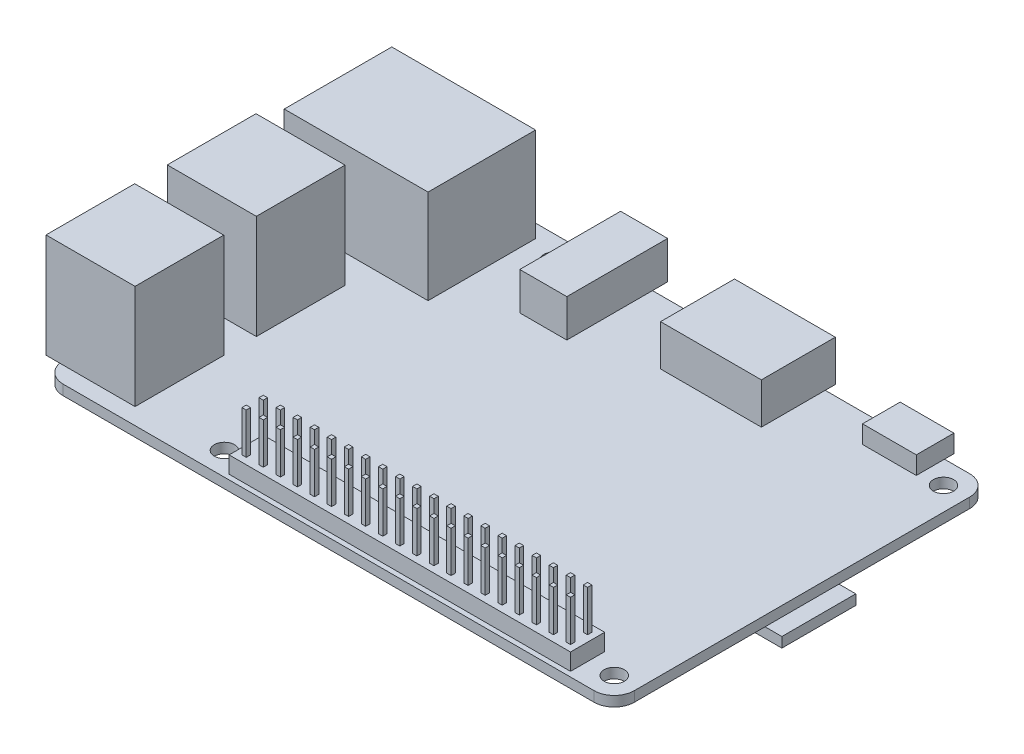
SolidWorks part; units mm, degrees
ref_plane "Front Plane" through (0, 0, 0) normal (0, 0, 1) x (1, 0, 0)
ref_plane "Top Plane" through (0, 0, 0) normal (0, 1, 0) x (1, 0, 0)
ref_plane "Right Plane" through (0, 0, 0) normal (1, 0, 0) x (0, 0, -1)
sketch "Sketch1" plane through (0, 0, 0) normal (0, 1, 0) x (1, 0, 0)
  line L0 (39.05, 24.5) -> (39.05, 27.95) construction
  line L1 (-39.5, -27.95) -> (39.5, -27.95)
  line L2 (-42.5, -24.95) -> (-42.5, 24.95)
  line L3 (-39.5, 27.95) -> (39.5, 27.95)
  line L4 (42.5, -24.95) -> (42.5, 24.95)
  line L5 (-42.5, -27.95) -> (42.5, 27.95) construction
  line L6 (-42.5, 27.95) -> (42.5, -27.95) construction
  line L7 (-18.95, -24.5) -> (39.05, -24.5) construction
  line L8 (-18.95, -24.5) -> (-18.95, 24.5) construction
  line L9 (-18.95, 24.5) -> (39.05, 24.5) construction
  line L10 (39.05, -24.5) -> (39.05, 24.5) construction
  line L11 (39.05, -24.5) -> (39.05, -27.95) construction
  line L12 (39.05, 24.5) -> (42.5, 24.5) construction
  circle A0 centre (-18.95, 24.5) radius 1.5
  circle A1 centre (39.05, 24.5) radius 1.5
  circle A2 centre (39.05, -24.5) radius 1.5
  circle A3 centre (-18.95, -24.5) radius 1.5
  arc A4 (39.5, 27.95) -> (42.5, 24.95) centre (39.5, 24.95) cw
  arc A5 (39.5, -27.95) -> (42.5, -24.95) centre (39.5, -24.95) ccw
  arc A6 (-39.5, -27.95) -> (-42.5, -24.95) centre (-39.5, -24.95) cw
  arc A7 (-42.5, 24.95) -> (-39.5, 27.95) centre (-39.5, 24.95) cw
  point P0 (0, 0)
  point P6 (0, 0)
  dimension "D1" = 3
  dimension "D6" = 3
  dimension "D2" = 85
  dimension "D3" = 55.9
  dimension "D4" = 49
  dimension "D5" = 58
extrude "Boss-Extrude1" add sketch "Sketch1" along normal blind 1.5
sketch "Sketch2" plane through (0, 0, 0) normal (0, -1, 0) x (1, 0, 0)
  line L0 (0, 0) -> (37.25, 0) construction
  line L1 (29.5, -5.5) -> (45, -5.5)
  line L2 (29.5, -5.5) -> (29.5, 5.5)
  line L3 (29.5, 5.5) -> (45, 5.5)
  line L4 (45, -5.5) -> (45, 5.5)
  line L5 (29.5, -5.5) -> (45, 5.5) construction
  line L6 (29.5, 5.5) -> (45, -5.5) construction
  line L7 (42.5, 24.95) -> (42.5, -24.95) construction
  point P0 (37.25, 0)
  dimension "D1" = 11
  dimension "D2" = 2.5
  dimension "D3" = 15.5
extrude "Boss-Extrude2" add sketch "Sketch2" along normal blind 1.5
sketch "Sketch3" plane through (0, 1.5, 0) normal (0, 1, 0) x (1, 0, 0)
  line L0 (39.5, 27.95) -> (-39.5, 27.95) construction
  line L1 (-44.5, 25.95) -> (-23.1, 25.95)
  line L2 (-44.5, 25.95) -> (-44.5, 9.95)
  line L3 (-44.5, 9.95) -> (-23.1, 9.95)
  line L4 (-23.1, 25.95) -> (-23.1, 9.95)
  line L5 (-42.5, 24.95) -> (-42.5, -24.95) construction
  dimension "D1" = 21.4
  dimension "D2" = 16
  dimension "D3" = 2
  dimension "D4" = 2
extrude "Boss-Extrude3" add sketch "Sketch3" along normal blind 14
sketch "Sketch4" plane through (0, 1.5, 0) normal (0, 1, 0) x (1, 0, 0)
  line L0 (-42.5, 9.95) -> (-23.1, 9.95) construction
  line L1 (-44.5, 5.75) -> (-31.25, 5.75)
  line L2 (-44.5, 5.75) -> (-44.5, -7.45)
  line L3 (-44.5, -7.45) -> (-31.25, -7.45)
  line L4 (-31.25, 5.75) -> (-31.25, -7.45)
  line L5 (-44.5, -12.3) -> (-31.25, -12.3)
  line L6 (-44.5, -12.3) -> (-44.5, -25.5)
  line L7 (-44.5, -25.5) -> (-31.25, -25.5)
  line L8 (-31.25, -12.3) -> (-31.25, -25.5)
  line L9 (-44.5, 25.95) -> (-44.5, 9.95) construction
  dimension "D1" = 4.2
  dimension "D2" = 13.2
  dimension "D3" = 4.85
  dimension "D4" = 13.25
extrude "Boss-Extrude4" add sketch "Sketch4" along normal blind 15.5
sketch "Sketch5" plane through (0, 1.5, 0) normal (0, 1, 0) x (1, 0, 0)
  line L0 (39.5, 27.95) -> (-39.5, 27.95) construction
  line L1 (18, 18.45) -> (3, 18.45)
  line L2 (18, 18.45) -> (18, 29.45)
  line L3 (18, 29.45) -> (3, 29.45)
  line L4 (3, 18.45) -> (3, 29.45)
  line L5 (42.5, -24.95) -> (42.5, 24.95) construction
  dimension "D1" = 1.5
  dimension "D2" = 15
  dimension "D3" = 11
  dimension "D4" = 24.5
extrude "Boss-Extrude5" add sketch "Sketch5" along normal blind 6.1 contours L1 L4 L3 L2
sketch "Sketch6" plane through (0, 1.5, 0) normal (0, 1, 0) x (1, 0, 0)
  line L0 (3, 27.95) -> (-39.5, 27.95) construction
  line L1 (-14.7, 15.2) -> (-7.7, 15.2)
  line L2 (-14.7, 15.2) -> (-14.7, 30.2)
  line L3 (-14.7, 30.2) -> (-7.7, 30.2)
  line L4 (-7.7, 15.2) -> (-7.7, 30.2)
  line L5 (-23.1, 9.95) -> (-23.1, 25.95) construction
  dimension "D1" = 7
  dimension "D2" = 15
  dimension "D3" = 2.25
  dimension "D4" = 8.4
extrude "Boss-Extrude6" add sketch "Sketch6" along normal blind 5.6
sketch "Sketch7" plane through (0, 1.5, 0) normal (0, 1, 0) x (1, 0, 0)
  line L0 (39.5, 27.95) -> (18, 27.95) construction
  line L1 (27.75, 23.75) -> (35.75, 23.75)
  line L2 (27.75, 23.75) -> (27.75, 29.35)
  line L3 (27.75, 29.35) -> (35.75, 29.35)
  line L4 (35.75, 23.75) -> (35.75, 29.35)
  line L5 (42.5, -24.95) -> (42.5, 24.95) construction
  dimension "D1" = 8
  dimension "D2" = 5.6
  dimension "D3" = 1.4
  dimension "D4" = 6.75
extrude "Boss-Extrude7" add sketch "Sketch7" along normal blind 2.66 contours L1 L4 L3 L2
sketch "Sketch8" plane through (0, 1.5, 0) normal (0, 1, 0) x (1, 0, 0)
  line L0 (42.5, -24.95) -> (42.5, 24.95) construction
  line L1 (35.27, -27.22) -> (32.73, -27.22)
  line L2 (35.27, -27.22) -> (35.27, -24.68)
  line L3 (35.27, -24.68) -> (32.73, -24.68)
  line L4 (32.73, -27.22) -> (32.73, -24.68)
  line L5 (35.27, -27.22) -> (32.73, -24.68) construction
  line L6 (35.27, -24.68) -> (32.73, -27.22) construction
  line L7 (34.32, -26.27) -> (33.68, -26.27)
  line L8 (34.32, -26.27) -> (34.32, -25.63)
  line L9 (34.32, -25.63) -> (33.68, -25.63)
  line L10 (33.68, -26.27) -> (33.68, -25.63)
  line L11 (34.32, -26.27) -> (33.68, -25.63) construction
  line L12 (34.32, -25.63) -> (33.68, -26.27) construction
  line L13 (-39.5, -27.95) -> (39.5, -27.95) construction
  point P0 (34, -25.95)
  point P5 (34, -25.95)
  dimension "D1" = 8.5
  dimension "D2" = 0.64
  dimension "D3" = 2.54
  dimension "D4" = 2
extrude "Boss-Extrude8" add sketch "Sketch8" along normal blind 2.5 contours L1 L4 L3 L2
extrude "Boss-Extrude9" add sketch "Sketch8<3>" along normal blind 8.6 contours L10 L7 L8 L9 region at (34, 1.5, 25.95)
sketch "Sketch8<3>" plane through (0, 1.5, 0) normal (0, 1, 0) x (1, 0, 0) same geometry as "Sketch8"
pattern_linear "LPattern1" count 20 spacing 2.54 along (-1, 0, 0) count 2 spacing 2.54 along (0, 0, -1) of "Boss-Extrude8", "Boss-Extrude9"
